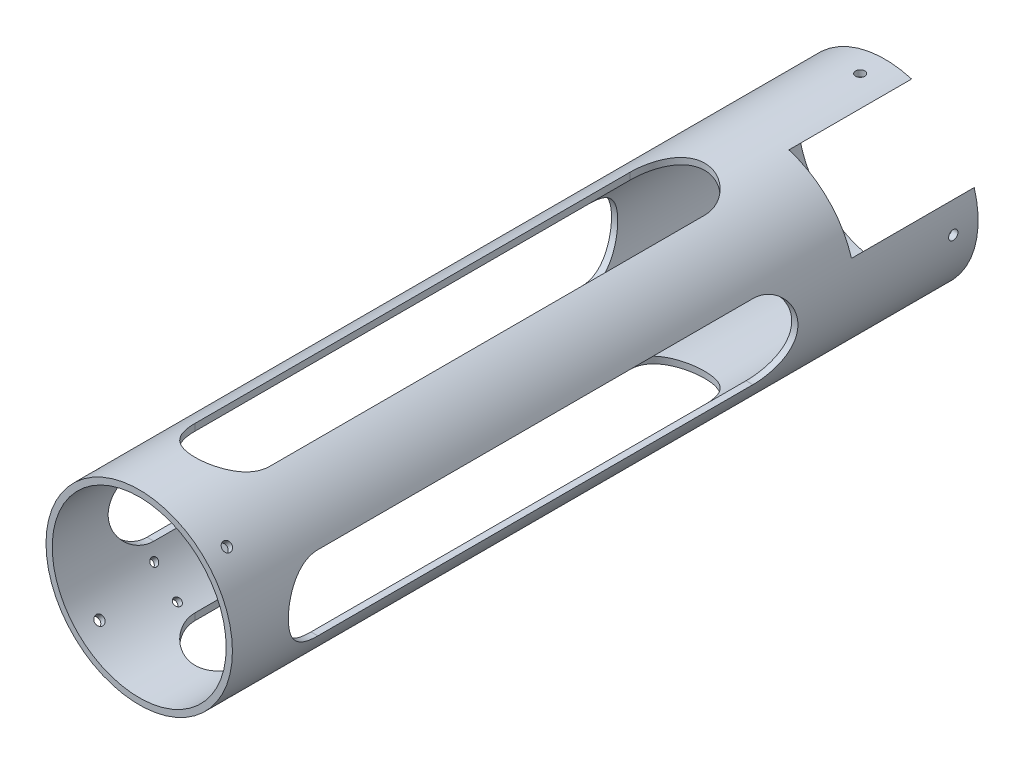
SolidWorks part; units mm, degrees
material "연성 주철 (SN)"
ref_plane "정면" through (0, 0, 0) normal (0, 0, 1) x (1, 0, 0)
ref_plane "윗면" through (0, 0, 0) normal (0, 1, 0) x (1, 0, 0)
ref_plane "우측면" through (0, 0, 0) normal (1, 0, 0) x (0, 0, -1)
sketch "스케치1" plane through (0, 0, 0) normal (0, 0, 1) x (1, 0, 0)
  circle A0 centre (0, 0) radius 28
  circle A1 centre (0, 0) radius 30
extrude "보스-돌출1" add sketch "스케치1" along normal blind 240
sketch "스케치2" plane through (24.9255, 24.9255, 0) normal (0.7071, 0.7071, 0) x (0, 0, -1)
  line L0 (0, -30) -> (0, 30) construction
  line L1 (-39.5, 14.25) -> (0, 14.25)
  line L2 (-39.5, 14.25) -> (-39.5, -14.25)
  line L3 (-39.5, -14.25) -> (0, -14.25)
  line L4 (0, 14.25) -> (0, -14.25)
extrude "컷-돌출1" cut sketch "스케치2" against normal blind 50
sketch "스케치3" plane through (14.4957, -14.4957, 0) normal (0.7071, -0.7071, 0) x (0, 0, -1)
  line L0 (-240, 28) -> (-240, -28) construction
  circle A0 centre (-233, 0) radius 1.5
  dimension "D1" = 7
extrude "컷-돌출2" cut sketch "스케치3" against normal through all both and the other way through all
sketch "스케치4" plane through (-21.2132, -21.2132, 0) normal (-0.7071, -0.7071, 0) x (0, 0, 1)
  line L0 (240, -30) -> (240, 30) construction
  circle A0 centre (233, 0) radius 1.5
  dimension "D1" = 7
extrude "컷-돌출3" cut sketch "스케치4" against normal through all both and the other way through all
ref_axis "기준축1" through (-84.8912, 0, 8) along (-1, 0, 0)
sketch "스케치5" plane through (0, 0, 240) normal (0, 0, 1) x (1, 0, 0)
  line L1 (11.3359, 33.3514) -> (-33.3514, 11.3359) construction
  line L2 (-33.3514, 11.3359) -> (-11.3359, -33.3514) construction
  line L3 (-11.3359, -33.3514) -> (33.3514, -11.3359) construction
  line L4 (33.3514, -11.3359) -> (11.3359, 33.3514) construction
  circle A0 centre (0, 0) radius 24.908 construction
sketch "스케치6" plane through (0, 0, 0) normal (0, 0, -1) x (-1, 0, 0)
  line L1 (33.0486, 33.1134) -> (-33.1134, 33.0486) construction
  line L2 (-33.1134, 33.0486) -> (-33.0486, -33.1134) construction
  line L3 (-33.0486, -33.1134) -> (33.1134, -33.0486) construction
  line L4 (33.1134, -33.0486) -> (33.0486, 33.1134) construction
  circle A0 centre (0, 0) radius 33.081 construction
sketch "스케치10" plane through (-9.3692, -9.3692, 0) normal (-0.7071, -0.7071, 0) x (0, 0, 1)
  circle A0 centre (30, -5.25) radius 1.25
  circle A1 centre (30, 5.25) radius 1.25
extrude "컷-돌출6" cut sketch "스케치10" along normal blind 32
sketch "스케치12" plane through (-9.3692, -9.3692, 0) normal (-0.7071, -0.7071, 0) x (0, 0, 1)
  circle A0 centre (212, -5.25) radius 1.25
  circle A1 centre (212, 5.25) radius 1.25
extrude "컷-돌출8" cut sketch "스케치12" against normal blind 6 and the other way through all
ref_plane "평면5" through (-33.1134, -33.0486, 0) normal (0.001, 1, 0) x (1, -0.001, 0)
ref_plane "평면6" through (-33.1134, -33.0486, 0) normal (-1, 0.001, 0) x (0, 0, 1)
sketch "스케치16" plane through (-33.1134, -33.0486, 0) normal (0.001, 1, 0) x (1, -0.001, 0)
  line L0 (3.081, 0) -> (3.081, -240) construction
  line L1 (66.1621, 0) -> (0, 0) construction
  circle A0 centre (33.081, -8) radius 1.5
  dimension "D1" = 30
  dimension "D2" = 8
extrude "컷-돌출9" cut sketch "스케치16" along normal through all
sketch "스케치17" plane through (-33.1134, -33.0486, 0) normal (-1, 0.001, 0) x (0, 0, 1)
  line L0 (9.5, 3.081) -> (240, 3.081) construction
  line L1 (0, 66.1621) -> (0, 0) construction
  circle A0 centre (8, 33.081) radius 1.5
  dimension "D1" = 30
  dimension "D2" = 8
extrude "컷-돌출10" cut sketch "스케치17" against normal through all
sketch "스케치24" plane through (0, 0, 0) normal (1, 0, 0) x (0, 0, -1)
  line L0 (-210, 0) -> (-70, 0) construction
  line L1 (36.6865, 0) -> (-36.6865, 0) construction
  line L2 (-210, 12) -> (-70, 12)
  line L3 (-210, -12) -> (-70, -12)
  line L4 (-240, 24.908) -> (-240, -24.908) construction
  arc A0 (-210, 12) -> (-210, -12) centre (-210, 0) ccw
  arc A1 (-70, -12) -> (-70, 12) centre (-70, 0) ccw
  point P5 (-140, 0)
  dimension "D1" = 12
  dimension "D2" = 30
  dimension "D3" = 140
extrude "컷-돌출14" cut sketch "스케치24" against normal through all both and the other way through all
sketch "스케치25" plane through (0, 0, 0) normal (0, 1, 0) x (1, 0, 0)
  line L0 (0, -210) -> (0, -70) construction
  line L1 (0, -36.6865) -> (0, 36.6865) construction
  line L2 (-12, -210) -> (-12, -70)
  line L3 (12, -210) -> (12, -70)
  line L4 (-24.908, -240) -> (24.908, -240) construction
  arc A0 (-12, -210) -> (12, -210) centre (0, -210) ccw
  arc A1 (12, -70) -> (-12, -70) centre (0, -70) ccw
  point P5 (0, -140)
  dimension "D3" = 12
  dimension "D1" = 30
  dimension "D2" = 140
extrude "컷-돌출15" cut sketch "스케치25" against normal through all both and the other way through all
